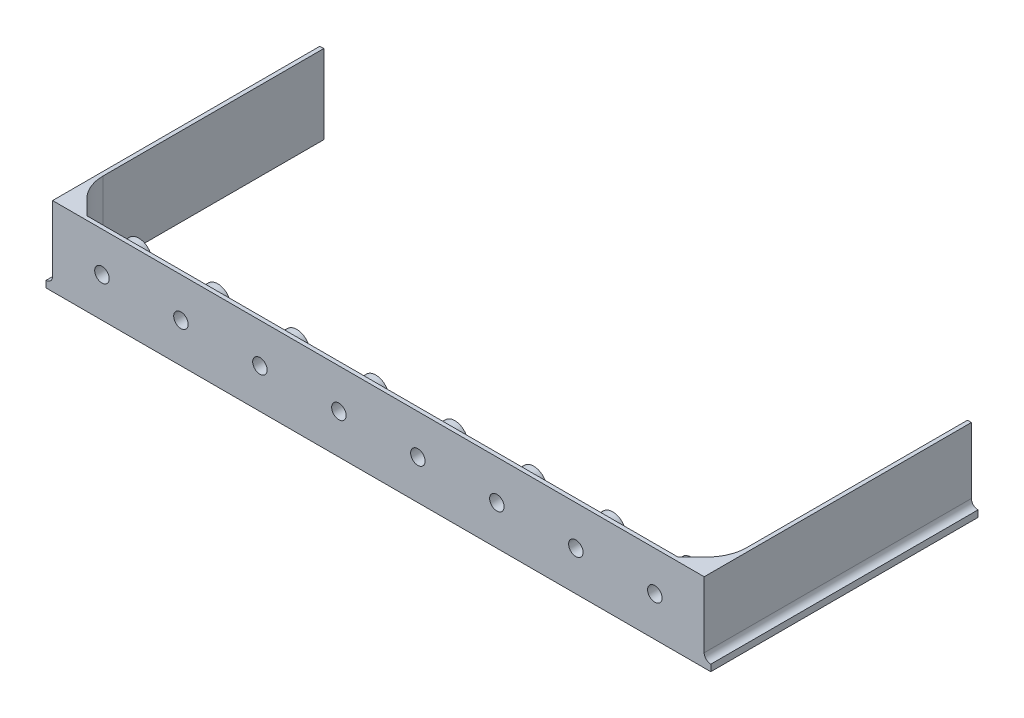
SolidWorks part; units mm, degrees
ref_plane "前视基准面" through (0, 0, 0) normal (0, 0, 1) x (1, 0, 0)
ref_plane "上视基准面" through (0, 0, 0) normal (0, 1, 0) x (1, 0, 0)
ref_plane "右视基准面" through (0, 0, 0) normal (1, 0, 0) x (0, 0, -1)
sketch "草图1" plane through (0, 0, 0) normal (0, 0, 1) x (1, 0, 0)
  line L1 (0, 0) -> (495, 0)
  line L2 (0, 0) -> (0, 60)
  line L3 (0, 60) -> (495, 60)
  line L4 (495, 0) -> (495, 60)
  dimension "D1" = 60
  dimension "D2" = 495
extrude "凸台-拉伸1" add sketch "草图1" along normal blind 3
sketch "草图2" plane through (0, 0, 0) normal (0, 0, -1) x (-1, 0, 0)
  line L0 (0, 0) -> (-495, 0) construction
  line L1 (-495, 60) -> (-492, 60)
  line L2 (-495, 60) -> (-495, 0)
  line L3 (-495, 0) -> (-492, 0)
  line L4 (-492, 60) -> (-492, 0)
  line L6 (0, 60) -> (-3, 60)
  line L7 (0, 60) -> (0, 0)
  line L8 (0, 0) -> (-3, 0)
  line L9 (-3, 60) -> (-3, 0)
  dimension "D1" = 3
  dimension "D2" = 3
extrude "凸台-拉伸2" add sketch "草图2" along normal blind 200
sketch "草图3" plane through (0, 0, 0) normal (0, -1, 0) x (1, 0, 0)
  line L0 (3, -20) -> (23, 0)
  line L1 (3, -200) -> (3, 0) construction
  line L2 (3, 0) -> (492, 0) construction
  line L3 (23, 0) -> (3, 0)
  line L4 (3, 0) -> (3, -20)
  line L5 (472, 0) -> (492, 0)
  line L6 (492, 0) -> (492, -20)
  line L7 (492, -200) -> (492, 0) construction
  line L8 (492, -20) -> (472, 0)
  dimension "D1" = 20
  dimension "D2" = 20
  dimension "D3" = 20
  dimension "D4" = 20
extrude "凸台-拉伸3" add sketch "草图3" against normal blind 60
sketch "草图4" plane through (0, 0, 0) normal (0, 0, -1) x (-1, 0, 0)
  line L0 (-472, 30) -> (-23, 30) construction
  line L1 (-472, 60) -> (-472, 0) construction
  line L2 (-23, 60) -> (-23, 0) construction
  line L3 (-495, 60) -> (-495, 0) construction
  circle A0 centre (-457.5, 30) radius 10
  dimension "D1" = 20
  dimension "D2" = 37.5
extrude "凸台-拉伸4" add sketch "草图4" along normal blind 25
sketch "草图5" plane through (0, 0, -25) normal (0, 0, -1) x (-1, 0, 0)
  circle A0 centre (-457.5, 30) radius 5.5
  dimension "D1" = 11
extrude "切除-拉伸1" cut sketch "草图5" against normal through all
pattern_linear "阵列(线性)1" count 8 spacing 60 along (-1, 0, 0) of "凸台-拉伸4", "切除-拉伸1"
fillet "圆角1" radius 30 2 edges at (492, 30, -20) (3, 30, -20)
sketch "草图6" plane through (0, 0, 0) normal (-1, 0, 0) x (0, 0, 1)
  line L0 (3, 60) -> (3, 0) construction
  line L6 (-200, 0) -> (3, 0)
  line L7 (-200, 0) -> (-200, 5)
  line L8 (-200, 5) -> (3, 5)
  line L9 (3, 0) -> (3, 5)
  dimension "D2" = 5
extrude "凸台-拉伸5" add sketch "草图6" along normal blind 5
sketch "草图7" plane through (495, 0, 0) normal (1, 0, 0) x (0, 0, -1)
  line L0 (200, 60) -> (200, 0) construction
  line L1 (-3, 0) -> (200, 0)
  line L2 (-3, 0) -> (-3, 5)
  line L3 (-3, 5) -> (200, 5)
  line L4 (200, 0) -> (200, 5)
  dimension "D1" = 5
extrude "凸台-拉伸6" add sketch "草图7" along normal blind 5
fillet "圆角2" radius 5 1 edges at (0, 5, -98.5)
fillet "圆角3" radius 5 1 edges at (495, 5, -98.5)
